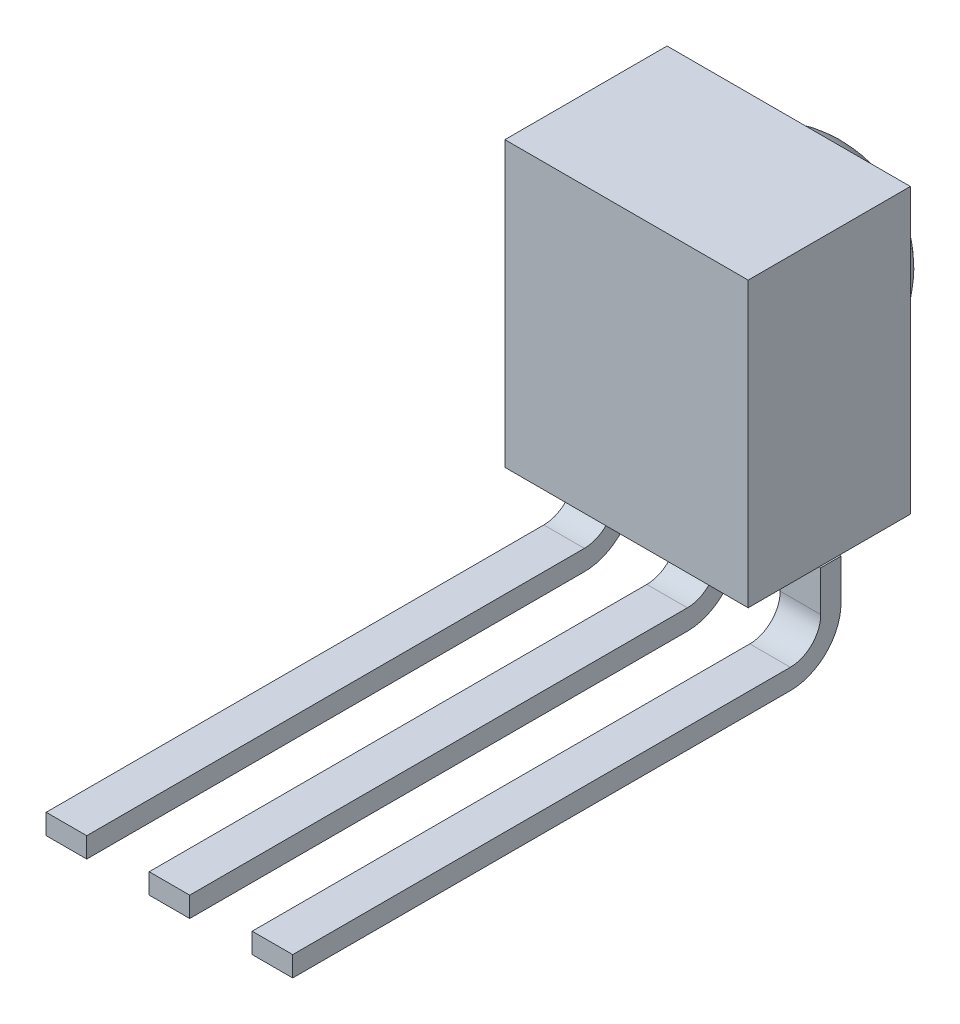
SolidWorks part; units mm, degrees
ref_plane "前视基准面" through (0, 0, 0) normal (0, 0, 1) x (1, 0, 0)
ref_plane "上视基准面" through (0, 0, 0) normal (0, 1, 0) x (1, 0, 0)
ref_plane "右视基准面" through (0, 0, 0) normal (1, 0, 0) x (0, 0, -1)
sketch "草图1" plane through (0, 0, 0) normal (0, 1, 0) x (1, 0, 0)
  line L0 (0, 12.7843) -> (0, -8.977) construction
  line L1 (-3, 2) -> (3, 2)
  line L2 (-3, 2) -> (-3, -2)
  line L3 (-3, -2) -> (3, -2)
  line L4 (3, 2) -> (3, -2)
  line L5 (6.3288, 0) -> (-6.536, 0) construction
  dimension "D1" = 6
  dimension "D2" = 4
extrude "拉伸1" add sketch "草图1" along normal blind 7
sketch "草图2" plane through (0, 0, -2) normal (0, 0, -1) x (-1, 0, 0)
  line L0 (0, 8.9947) -> (0, -2.7615) construction
  circle A0 centre (0, 4.0409) radius 2.5
  dimension "D1" = 5
extrude "拉伸2" add sketch "草图2" along normal blind 2
fillet "圆角1" radius 2.5 1 edges at (-2.5, 4.0409, -4)
sketch "草图3" plane through (0, 0, 0) normal (0, -1, 0) x (1, 0, 0)
  line L0 (4.2595, 0) -> (-4.83, 0) construction
  line L1 (0, -0.7677) -> (0, 0.7302) construction
  line L2 (0.5, 0.25) -> (-0.5, 0.25)
  line L3 (0.5, 0.25) -> (0.5, -0.25)
  line L4 (0.5, -0.25) -> (-0.5, -0.25)
  line L5 (-0.5, 0.25) -> (-0.5, -0.25)
  line L6 (3.04, 0.25) -> (2.04, 0.25)
  line L7 (3.04, 0.25) -> (3.04, -0.25)
  line L8 (3.04, -0.25) -> (2.04, -0.25)
  line L9 (2.04, 0.25) -> (2.04, -0.25)
  line L10 (2.54, -0.7677) -> (2.54, 0.7302) construction
  line L11 (-2.54, -0.7677) -> (-2.54, 0.7302) construction
  line L12 (-2.04, 0.25) -> (-2.04, -0.25)
  line L13 (-3.04, -0.25) -> (-2.04, -0.25)
  line L14 (-3.04, 0.25) -> (-3.04, -0.25)
  line L15 (-3.04, 0.25) -> (-2.04, 0.25)
  dimension "D1" = 1
  dimension "D2" = 0.5
  dimension "D3" = 2
  dimension "D4" = 5.08
sketch "草图4" plane through (0, 0, 0) normal (1, 0, 0) x (0, 0, -1)
  line L0 (0, 0) -> (0, -1)
  line L1 (-1, -2) -> (-13.2733, -2)
  line L2 (-2, 0) -> (2, 0) construction
  arc A0 (0, -1) -> (-1, -2) centre (-1, -1) cw
  dimension "D1" = 1
  dimension "D2" = 2
sweep "扫描1" add profiles "草图3" path "草图4"
ref_plane "基准面1" through (0, 4, 0) normal (0, 1, 0) x (1, 0, 0)
